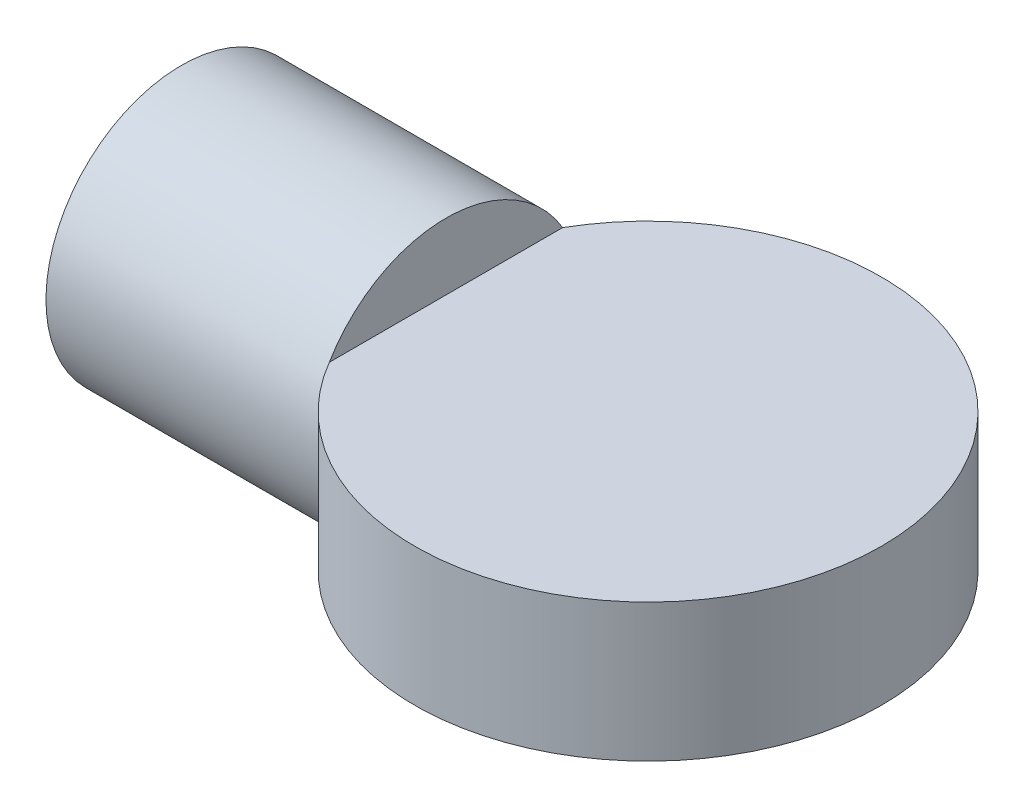
SolidWorks part; units mm, degrees
ref_plane "Front Plane" through (0, 0, 0) normal (0, 0, 1) x (1, 0, 0)
ref_plane "Top Plane" through (0, 0, 0) normal (0, 1, 0) x (1, 0, 0)
ref_plane "Right Plane" through (0, 0, 0) normal (1, 0, 0) x (0, 0, -1)
sketch "Sketch1" plane through (0, 0, 0) normal (0, 1, 0) x (1, 0, 0)
  line L0 (-50.8, 0) -> (-101.6, 0)
  line L1 (-101.6, 0) -> (-101.6, 25.4)
  line L2 (-101.6, 25.4) -> (-43.9941, 25.4)
  line L3 (-101.6, 0) -> (-101.6, -25.4)
  line L4 (-101.6, -25.4) -> (-43.9941, -25.4)
  circle A0 centre (0, 0) radius 50.8
extrude "Boss-Extrude1" add sketch "Sketch1" along normal blind 30 contours A0 L2 L1 L0 | A0 L0 L3 L4 | A0 region at (-75.0599, 0, 12.9677) region at (-75.0599, 0, -12.9677) region at (0, 0, 0)
ref_plane "Plane1" through (-43.9941, 30, 25.4) normal (0.5, 0, 0.866) x (0.866, 0, -0.5)
sketch "Sketch4" plane through (-101.6, 0, 0) normal (-1, 0, 0) x (0, 0, 1)
  line L0 (25.4, 30) -> (-25.4, 30) construction
  line L1 (25.4, 30) -> (25.4, 0) construction
  line L2 (-25.4, 30) -> (25.4, 30)
  line L3 (25.4, 0) -> (-25.4, 0)
  arc A1 (-25.4, 30) -> (25.4, 30) centre (0, 15) cw
  arc A2 (-25.4, 0) -> (25.4, 0) centre (0, 15) ccw
extrude "Boss-Extrude4" add sketch "Sketch4" against normal blind 57.6059
sketch "Sketch5" plane through (-101.6, 0, 0) normal (-1, 0, 0) x (0, 0, 1)
  line L0 (-50.8, 0) -> (50.8, 0) construction
  line L1 (-25.4, 30) -> (-25.4, 0)
  arc A0 (-25.4, 30) -> (-25.4, 0) centre (0, 15) ccw
  arc A1 (25.4, 30) -> (25.4, 0) centre (0, 15) cw
  line M3 (-25.4, 30) -> (-25.4, 0)
  line M5 (25.4, 0) -> (25.4, 30)
extrude "Boss-Extrude5" add sketch "Sketch5" against normal blind 60.6059 contours A1 M5 | A0 M3 region at (-101.6, 15, -27.0496) region at (-101.6, 15, 27.0496)
